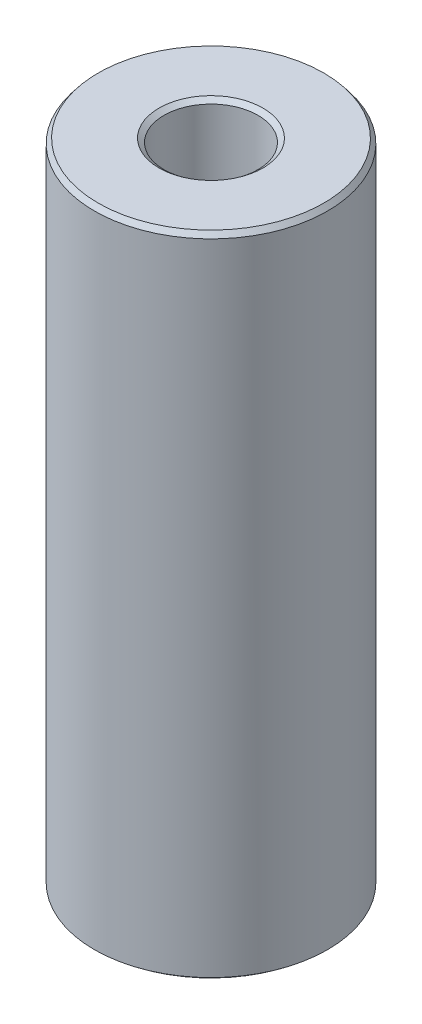
SolidWorks part; units mm, degrees
ref_plane "Front Plane" through (0, 0, 0) normal (0, 0, 1) x (1, 0, 0)
ref_plane "Top Plane" through (0, 0, 0) normal (0, 1, 0) x (1, 0, 0)
ref_plane "Right Plane" through (0, 0, 0) normal (1, 0, 0) x (0, 0, -1)
sketch "Sketch1" plane through (0, 0, 0) normal (0, 1, 0) x (1, 0, 0)
  circle A0 centre (0, 0) radius 55
  dimension "SLEEVE_OD" = 110
extrude "Boss-Extrude1" add sketch "Sketch1" along normal blind 305.9187
sketch "Sketch2" plane through (0, 0, 0) normal (0, 1, 0) x (1, 0, 0)
  circle A0 centre (0, 0) radius 22.1945
  dimension "BORE_D" = 44.389
extrude "Cut-Extrude1" cut sketch "Sketch2" along normal through all
chamfer "Chamfer1" distance 2.318 angle 37.864 4 edges at (0, 305.9187, 22.1945) (0, 0, 22.1945) (0, 0, 55) (0, 305.9187, 55) first distance on face at (0, 305.9187, 22.1945) first distance on face at (0, 0, 22.1945) first distance on face at (0, 305.9187, 55)
